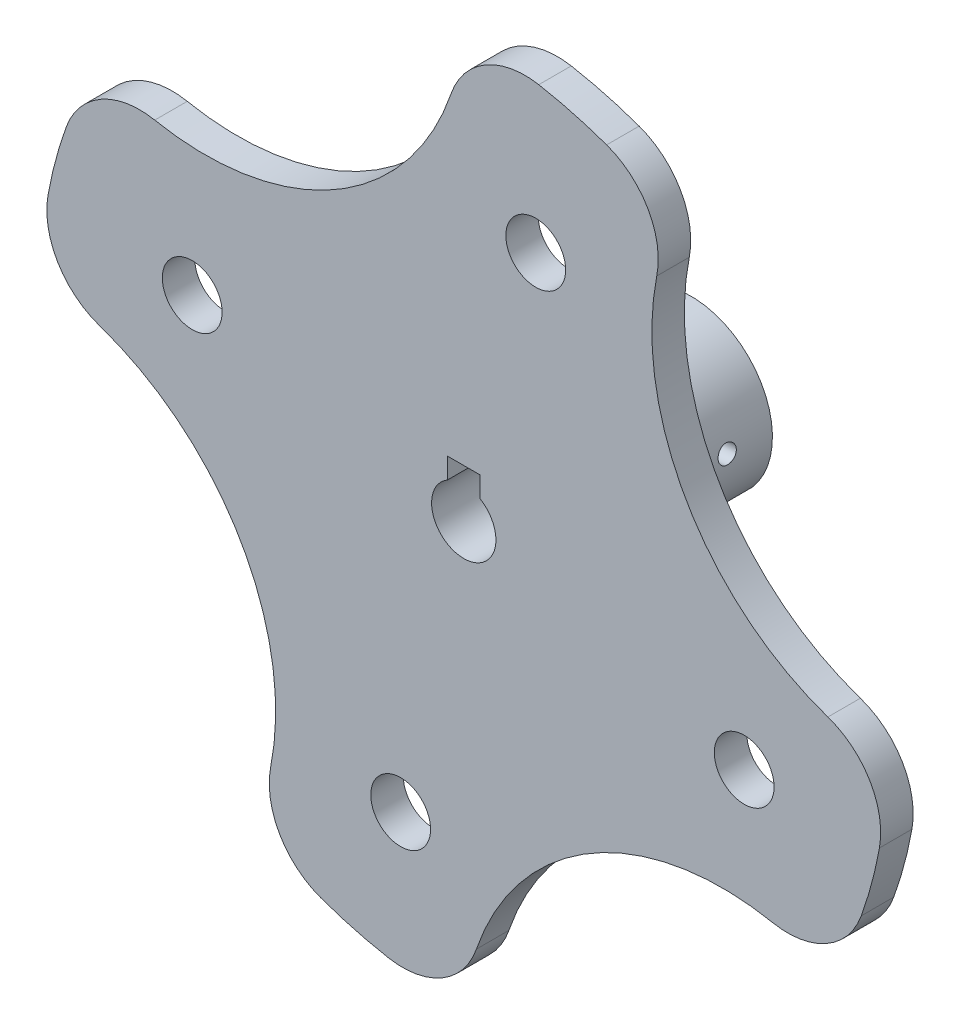
SolidWorks part; units mm, degrees
ref_plane "Front Plane" through (0, 0, 0) normal (0, 0, 1) x (1, 0, 0)
ref_plane "Top Plane" through (0, 0, 0) normal (0, 1, 0) x (1, 0, 0)
ref_plane "Right Plane" through (0, 0, 0) normal (1, 0, 0) x (0, 0, -1)
sketch "Sketch1" plane through (0, 0, 0) normal (0, 0, 1) x (1, 0, 0)
  circle A0 centre (0, 0) radius 65
  dimension "D1" = 130
extrude "Boss-Extrude1" add sketch "Sketch1" along normal blind 5
sketch "Sketch2" plane through (0, 0, 5) normal (0, 0, 1) x (1, 0, 0)
  line L1 (12.5, -7.2169) -> (12.5, 7.2169)
  line L2 (12.5, 7.2169) -> (0, 14.4338)
  line L3 (0, 14.4338) -> (-12.5, 7.2169)
  line L4 (-12.5, 7.2169) -> (-12.5, -7.2169)
  line L5 (-12.5, -7.2169) -> (0, -14.4338)
  line L6 (0, -14.4338) -> (12.5, -7.2169)
  circle A0 centre (0, 0) radius 12.5 construction
  dimension "D1" = 25
extrude "Boss-Extrude2" [suppressed] add sketch "Sketch2" along normal blind 5
sketch "Sketch3" [suppressed] plane through (0, 0, 10) normal (0, 0, 1) x (1, 0, 0)
  circle A0 centre (0, 0) radius 10
  dimension "D1" = 20
extrude "Boss-Extrude3" [suppressed] add sketch "Sketch3" along normal blind 25
fillet "Fillet1" [suppressed] radius 3
sketch "Sketch4" [suppressed] plane through (0, 0, 35) normal (0, 0, 1) x (1, 0, 0)
  circle A0 centre (0, 0) radius 4.95
  dimension "D1" = 9.9
extrude "Cut-Extrude1" [suppressed] cut sketch "Sketch4" against normal through all
hole_wizard "Ø1.0mm Dowel Hole1" [suppressed] positions "3DSketch1" profile "Sketch5" hole size "Ø1.0" standard "ANSI Metric"
sketch3d "3DSketch1" [suppressed]
  point P0 (-8.696, 4.9375, 25.8574)
  point P2 (4.8442, 8.7483, 25.3286)
sketch "Sketch5" plane through (-8.696, 4.9375, 25.8574) normal (0, 0, 1) x (-0.4938, -0.8696, 0)
  line L0 (0, 0) -> (0, 34)
  line L1 (0, 34) -> (1.4, 33.1588)
  line L2 (1.4, 33.1588) -> (1.4, 0)
  line L5 (1.4, 0) -> (0, 0)
  line L10 (0, 34) -> (-1.4, 33.1588) construction
  line L11 (0, -6.35) -> (0, 107.95) construction
  dimension "Hole Dia." = 2.8
  dimension "Hole Depth" = 34
  dimension "Drill Angle" = 118
sketch "Sketch6" plane through (0, 0, 5) normal (0, 0, 1) x (1, 0, 0)
  line L0 (0, 65) -> (0, 0) construction
  line L1 (0, 0) -> (-56.2917, 32.5) construction
  arc A1 (-32.5, -56.2917) -> (-65, 0) centre (-68.9444, -39.805) ccw
  arc A3 (-56.2917, 32.5) -> (0, 65) centre (-39.805, 68.9444) ccw
  circle A4 centre (0, 0) radius 65 construction
  arc A5 (32.5, 56.2917) -> (65, 0) centre (68.9444, 39.805) ccw
  arc A6 (56.2917, -32.5) -> (0, -65) centre (39.805, -68.9444) ccw
  circle A8 centre (0, 0) radius 65
  circle A9 centre (0, 0) radius 65
  point P8 (100.8796, 48.3276)
  point P9 (0, 0)
  point P15 (0, 0)
  point P16 (0, 0)
  dimension "D1" = 60
  dimension "D3" = 4
  dimension "D2" = 40
  dimension "D4" = 0
extrude "Cut-Extrude2" cut sketch "Sketch6" against normal blind 25
fillet "Fillet2" radius 12 8 edges at (56.2917, -32.5, 2.5) (0, -65, 2.5) (32.5, 56.2917, 2.5) (65, 0, 2.5) (-56.2917, 32.5, 2.5) (0, 65, 2.5) (-32.5, -56.2917, 2.5) (-65, 0, 2.5)
sketch "Sketch7" plane through (0, 0, 0) normal (0, 0, -1) x (-1, 0, 0)
  line L0 (-16.8232, 62.7852) -> (0, 0) construction
  arc A1 (-11.5417, 63.9671) -> (-21.9882, 61.168) centre (0, 0) ccw construction
  point P0 (-19.1344, 71.4105)
  point P1 (-17.3152, 78.1037)
  point P10 (72.2459, 16.0165)
  point P11 (16.852, -75.3638)
  point P12 (-74.5283, -19.9698)
  point P13 (-1.1412, -1.9766)
  dimension "D2" = 4
sketch "Sketch9" plane through (0, 0, 0) normal (0, 0, -1) x (-1, 0, 0)
  circle A0 centre (0, 0) radius 12.5
  dimension "D1" = 25
extrude "Boss-Extrude4" add sketch "Sketch9" along normal blind 30
fillet "Fillet3" [suppressed] radius 15
sketch "Sketch10" plane through (0, 0, -30) normal (0, 0, -1) x (-1, 0, 0)
  circle A0 centre (0, 0) radius 4.95
  dimension "D1" = 9.9
extrude "Cut-Extrude3" cut sketch "Sketch10" against normal through all
sketch "Sketch11" plane through (0, 0, -30) normal (0, 0, -1) x (-1, 0, 0)
  line L1 (-2.5, 2.45) -> (2.5, 2.45)
  line L2 (-2.5, 2.45) -> (-2.5, 7.45)
  line L3 (-2.5, 7.45) -> (2.5, 7.45)
  line L4 (2.5, 2.45) -> (2.5, 7.45)
  line L5 (-2.5, 2.45) -> (2.5, 7.45) construction
  line L6 (-2.5, 7.45) -> (2.5, 2.45) construction
  circle A0 centre (0, 0) radius 4.95 construction
  point P0 (0, 4.95)
  point P7 (0, 0)
  dimension "D1" = 5
  dimension "D2" = 5
extrude "Cut-Extrude4" cut sketch "Sketch11" against normal through all
hole_wizard "Ø1.0mm Dowel Hole3" positions "3DSketch3" profile "Sketch12" hole size "Ø1.0" standard "ANSI Metric"
sketch3d "3DSketch3"
  point P0 (8.5996, 9.0717, -22.4664)
  point P1 (12.4474, 1.1452, -23.0939)
  point P3 (0, -12.5, -18.5782)
  point P7 (0, 0, -14.3952)
  point P10 (1.4675, -12.4136, -18.613)
  point P11 (0, 0, 0)
  point P12 (-0.0372, -12.4999, -18.5782)
sketch "Sketch12" plane through (0, -12.5, -18.5782) normal (1, 0, 0) x (0, 0, -1)
  line L0 (0, 0) -> (0, 34)
  line L1 (0, 34) -> (1.4, 33.1588)
  line L2 (1.4, 33.1588) -> (1.4, 0)
  line L5 (1.4, 0) -> (0, 0)
  line L10 (0, 34) -> (-1.4, 33.1588) construction
  line L11 (0, -6.35) -> (0, 107.95) construction
  dimension "Hole Dia." = 2.8
  dimension "Hole Depth" = 34
  dimension "Drill Angle" = 118
sketch "Sketch13" plane through (0, 0, 0) normal (0, 0, -1) x (-1, 0, 0)
  circle A0 centre (0, 0) radius 33
  dimension "D1" = 66
extrude "Boss-Extrude5" add sketch "Sketch13" along normal blind 4 and the other way up to surface (5 mm away) other way up to face at (0, 3.5556, 5)
sketch "Sketch15" plane through (0, 0, 0) normal (0, 0, -1) x (-1, 0, 0)
  line L0 (-16.8232, 62.7852) -> (0, 0) construction
  point P0 (-11.0775, 41.3416)
  point P1 (41.7855, 9.2636)
  point P2 (-43.1555, -11.5213)
  point P8 (9.7075, -43.5993)
  point P9 (-0.685, -1.1288)
  dimension "D1" = 42.8
  dimension "D2" = 4
hole_wizard "Ø1.0mm Dowel Hole4" positions "3DSketch4" profile "Sketch16" hole size "Ø1.0" standard "ANSI Metric"
sketch3d "3DSketch4"
  point P0 (11.0775, 41.3416, 0)
  point P5 (-9.7075, -43.5993, 0)
  point P11 (-41.7855, 9.2636, 0)
  point P14 (43.1555, -11.5213, 0)
sketch "Sketch16" plane through (11.0775, 41.3416, 0) normal (1, 0, 0) x (0, 1, 0)
  line L0 (0, 0) -> (0, 34)
  line L1 (0, 34) -> (4.6, 31.236)
  line L2 (4.6, 31.236) -> (4.6, 0)
  line L5 (4.6, 0) -> (0, 0)
  line L10 (0, 34) -> (-4.6, 31.236) construction
  line L11 (0, -6.35) -> (0, 107.95) construction
  dimension "Hole Dia." = 9.2
  dimension "Hole Depth" = 34
  dimension "Drill Angle" = 118
fillet "Fillet4" radius 15 1 edges at (-12.5, 0, -4)
sketch "Sketch17" plane through (0, 0, -30) normal (0, 0, -1) x (-1, 0, 0)
  line L3 (2.5, 4.2723) -> (2.5, 7.45)
  line L4 (2.5, 7.45) -> (-2.5, 7.45)
  line L5 (-2.5, 7.45) -> (-2.5, 4.2723)
  line L6 (2.5, 4.2723) -> (2.5, 7.45)
  line L7 (2.5, 7.45) -> (-2.5, 7.45)
  line L8 (-2.5, 7.45) -> (-2.5, 4.2723)
  arc A1 (-2.5, 4.2723) -> (2.5, 4.2723) centre (0, 0) ccw
  arc A2 (-2.5, 4.2723) -> (2.5, 4.2723) centre (0, 0) ccw
  dimension "D1" = 0
extrude "Cut-Extrude5" cut sketch "Sketch17" against normal through all
hole_wizard "Ø1.0mm Dowel Hole2" positions "3DSketch2" profile "Sketch8" hole size "Ø1.0" standard "ANSI Metric"
sketch3d "3DSketch2"
  point P0 (5.7432, 43.6236, 0)
  point P3 (-43.6236, 5.7432, 0)
  point P6 (-5.7432, -43.6236, 0)
  point P9 (43.6236, -5.7432, 0)
sketch "Sketch8" plane through (5.7432, 43.6236, 0) normal (1, 0, 0) x (0, 1, 0)
  line L0 (0, 0) -> (0, 34)
  line L1 (0, 34) -> (1.7, 32.9785)
  line L2 (1.7, 32.9785) -> (1.7, 0)
  line L5 (1.7, 0) -> (0, 0)
  line L10 (0, 34) -> (-1.7, 32.9785) construction
  line L11 (0, -6.35) -> (0, 107.95) construction
  dimension "Hole Dia." = 3.4
  dimension "Hole Depth" = 34
  dimension "Drill Angle" = 118
